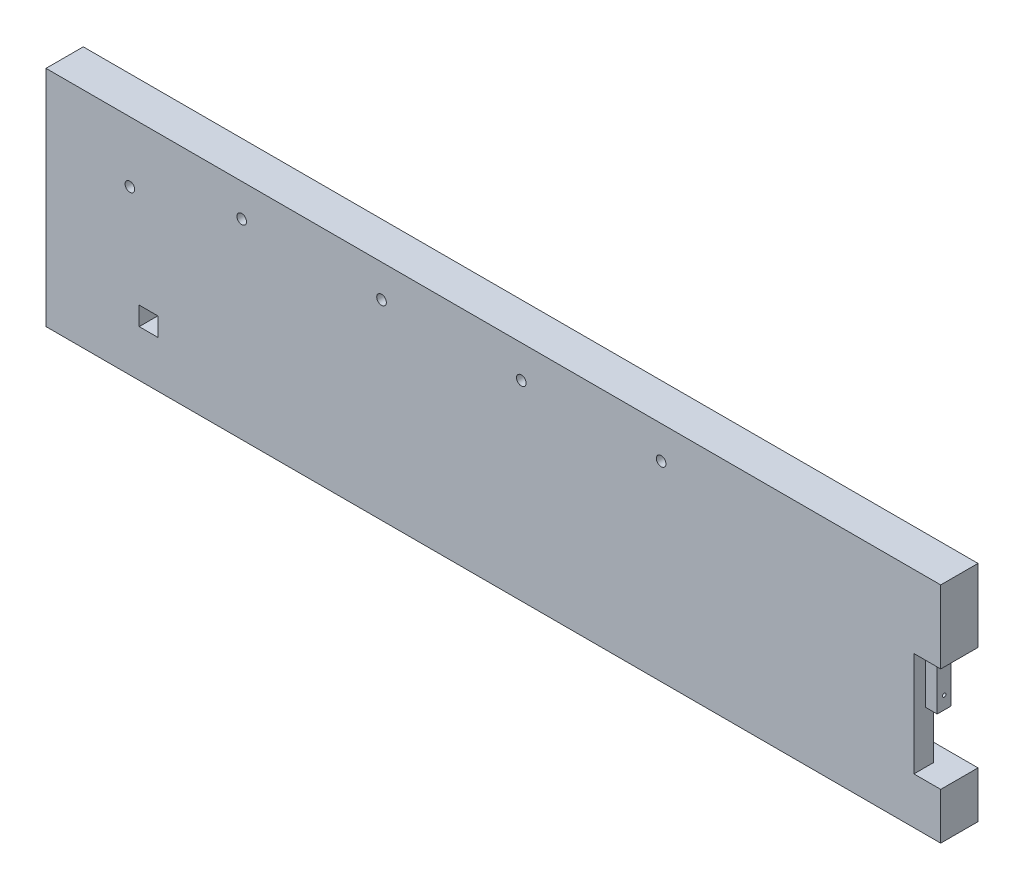
SolidWorks part; units mm, degrees
material "Pine"
ref_plane "Front Plane" through (0, 0, 0) normal (0, 0, 1) x (1, 0, 0)
ref_plane "Top Plane" through (0, 0, 0) normal (0, 1, 0) x (1, 0, 0)
ref_plane "Right Plane" through (0, 0, 0) normal (1, 0, 0) x (0, 0, -1)
sketch "Sketch1" plane through (0, 0, 0) normal (0, 0, 1) x (1, 0, 0)
  line L1 (1219.2, 304.8) -> (-1219.2, 304.8)
  line L2 (1219.2, 304.8) -> (1219.2, -304.8)
  line L3 (1219.2, -304.8) -> (-1219.2, -304.8)
  line L4 (-1219.2, 304.8) -> (-1219.2, -304.8)
  line L5 (1219.2, 304.8) -> (-1219.2, -304.8) construction
  line L6 (1219.2, -304.8) -> (-1219.2, 304.8) construction
  line L7 (-965.2, -127) -> (-914.4, -127)
  line L8 (-965.2, -127) -> (-965.2, -177.8)
  line L9 (-965.2, -177.8) -> (-914.4, -177.8)
  line L10 (-914.4, -127) -> (-914.4, -177.8)
  line L11 (-965.2, -127) -> (-914.4, -177.8) construction
  line L12 (-965.2, -177.8) -> (-914.4, -127) construction
  circle A0 centre (-990.6, 139.7) radius 13.1198
  circle A1 centre (-685.8, 215.9) radius 13.1198
  circle A2 centre (-304.8, 215.9) radius 13.1198
  circle A3 centre (76.2, 215.9) radius 13.1198
  circle A4 centre (457.2, 215.9) radius 13.1198
  point P0 (0, 0)
  point P10 (-939.8, -152.4)
  dimension "D10" = 381
  dimension "D11" = 381
  dimension "D12" = 381
  dimension "D1" = 609.6
  dimension "D2" = 2438.4
  dimension "D3" = 88.9
  dimension "D4" = 228.6
  dimension "D5" = 304.8
  dimension "D6" = 165.1
  dimension "D7" = 127
  dimension "D8" = 50.8
  dimension "D9" = 254
extrude "Boss-Extrude1" add sketch "Sketch1" along normal blind 101.6
sketch "Sketch2" plane through (0, 0, 0) normal (0, 0, -1) x (-1, 0, 0)
  line L0 (1219.2, -304.8) -> (-1219.2, -304.8) construction
  line L1 (711.2, -288.925) -> (-711.2, -288.925)
  line L2 (711.2, -288.925) -> (711.2, -273.05)
  line L3 (711.2, -273.05) -> (-711.2, -273.05)
  line L4 (-711.2, -288.925) -> (-711.2, -273.05)
  line L5 (711.2, -288.925) -> (-711.2, -273.05) construction
  line L6 (711.2, -273.05) -> (-711.2, -288.925) construction
  line L7 (1219.2, 304.8) -> (1219.2, -304.8) construction
  line L9 (711.2, -273.05) -> (838.2, -273.05)
  line L10 (711.2, -273.05) -> (711.2, -209.55)
  line L11 (711.2, -209.55) -> (838.2, -209.55)
  line L12 (838.2, -273.05) -> (838.2, -209.55)
  line L13 (711.2, -273.05) -> (838.2, -209.55) construction
  line L14 (711.2, -209.55) -> (838.2, -273.05) construction
  line L15 (838.2, 209.55) -> (711.2, 209.55)
  line L16 (838.2, 209.55) -> (838.2, 273.05)
  line L17 (838.2, 273.05) -> (711.2, 273.05)
  line L18 (711.2, 209.55) -> (711.2, 273.05)
  line L19 (838.2, 209.55) -> (711.2, 273.05) construction
  line L20 (838.2, 273.05) -> (711.2, 209.55) construction
  line L21 (-838.2, -273.05) -> (-711.2, -273.05)
  line L22 (-838.2, -273.05) -> (-838.2, -209.55)
  line L23 (-838.2, -209.55) -> (-711.2, -209.55)
  line L24 (-711.2, -273.05) -> (-711.2, -209.55)
  line L25 (-838.2, -273.05) -> (-711.2, -209.55) construction
  line L26 (-838.2, -209.55) -> (-711.2, -273.05) construction
  line L27 (-711.2, 209.55) -> (-838.2, 209.55)
  line L28 (-711.2, 209.55) -> (-711.2, 273.05)
  line L29 (-711.2, 273.05) -> (-838.2, 273.05)
  line L30 (-838.2, 209.55) -> (-838.2, 273.05)
  line L31 (-711.2, 209.55) -> (-838.2, 273.05) construction
  line L32 (-711.2, 273.05) -> (-838.2, 209.55) construction
  point P0 (0, -280.9875)
  point P9 (774.7, -241.3)
  point P14 (774.7, 241.3)
  point P19 (-774.7, -241.3)
  point P24 (-774.7, 241.3)
  point P29 (711.2, -241.3)
  dimension "D1" = 15.875
  dimension "D2" = 15.875
  dimension "D3" = 508
  dimension "D4" = 1422.4
  dimension "D5" = 95.25
  dimension "D6" = 508
  dimension "D7" = 15.875
  dimension "D8" = 419.1
  dimension "D9" = 15.875
  dimension "D10" = 127
  dimension "D11" = 63.5
  dimension "D12" = 127
  dimension "D13" = 63.5
  dimension "D14" = 63.5
  dimension "D15" = 127
extrude "Cut-Extrude1" cut sketch "Sketch2" against normal blind 50.8 contours L18 L15 L16 L17 | L9 L12 L11 L10 | L30 L27 L28 L29 | L21 L24 L23 L22 region at (774.7, -241.3, 0) region at (-774.7, -241.3, 0) region at (-774.7, 241.3, 0) region at (774.7, 241.3, 0)
sketch "Sketch3" plane through (0, -304.8, 0) normal (0, -1, 0) x (1, 0, 0)
  line L0 (711.2, 0) -> (838.2, 0) construction
  line L1 (838.2, 0) -> (838.2, 50.8) construction
  line L2 (838.2, 50.8) -> (711.2, 50.8) construction
  line L3 (711.2, 50.8) -> (711.2, 0) construction
  line L4 (-838.2, 0) -> (-711.2, 0) construction
  line L5 (-711.2, 0) -> (-711.2, 50.8) construction
  line L6 (-711.2, 50.8) -> (-838.2, 50.8) construction
  line L7 (-838.2, 50.8) -> (-838.2, 0) construction
  line L8 (711.2, 0) -> (838.2, 0)
  line L9 (838.2, 0) -> (838.2, 50.8)
  line L10 (838.2, 50.8) -> (711.2, 50.8)
  line L11 (711.2, 50.8) -> (711.2, 0)
  line L12 (-838.2, 0) -> (-711.2, 0)
  line L13 (-711.2, 0) -> (-711.2, 50.8)
  line L14 (-711.2, 50.8) -> (-838.2, 50.8)
  line L15 (-838.2, 50.8) -> (-838.2, 0)
  line L16 (-838.2, 25.4) -> (-711.2, 25.4) construction
  line L17 (711.2, 25.4) -> (838.2, 25.4) construction
  circle A0 centre (-742.95, 25.4) radius 4.7625
  circle A1 centre (-806.45, 25.4) radius 4.7625
  circle A2 centre (742.95, 25.4) radius 4.7625
  circle A3 centre (806.45, 25.4) radius 4.7625
  point P14 (-774.7, 25.4)
  point P21 (774.7, 25.4)
  dimension "D1" = 9.525
  dimension "D4" = 9.525
  dimension "D2" = 31.75
  dimension "D3" = 31.75
  dimension "D5" = 31.75
  dimension "D6" = 31.75
extrude "Cut-Extrude2" cut sketch "Sketch3" against normal blind 152.4 contours A3 | A2 | A0 | A1 region at (-742.95, -304.8, 25.4) region at (-806.45, -304.8, 25.4) region at (742.95, -304.8, 25.4) region at (806.45, -304.8, 25.4)
sketch "Sketch4" plane through (0, 0, 101.6) normal (0, 0, 1) x (1, 0, 0)
  line L0 (-1219.2, -304.8) -> (1219.2, -304.8) construction
  line L1 (1219.2, -177.8) -> (1146.175, -177.8)
  line L2 (1219.2, -177.8) -> (1219.2, 106.3625)
  line L3 (1219.2, 106.3625) -> (1146.175, 106.3625)
  line L4 (1146.175, -177.8) -> (1146.175, 106.3625)
  line L5 (1219.2, -304.8) -> (1219.2, 304.8) construction
  point P5 (0, 0)
  dimension "D1" = 73.025
  dimension "D2" = 284.1625
  dimension "D3" = 127
extrude "Cut-Extrude3" cut sketch "Sketch4" against normal through all
sketch "Sketch5" plane through (1146.175, 0, 0) normal (1, 0, 0) x (0, 0, -1)
  line L0 (-46.0375, 71.4375) -> (-46.0375, 76.2) construction
  line L1 (-55.5625, 76.2) -> (-55.5625, 71.4375) construction
  line L2 (-46.0375, 71.4375) -> (-46.0375, 76.2)
  line L3 (-55.5625, 76.2) -> (-55.5625, 71.4375)
  line L4 (-69.85, 87.3125) -> (-69.85, -36.5125)
  line L5 (-31.75, 87.3125) -> (-69.85, 87.3125)
  line L6 (-31.75, -36.5125) -> (-31.75, 87.3125)
  line L7 (-69.85, -36.5125) -> (-31.75, -36.5125)
  line L8 (-69.85, 87.3125) -> (-69.85, -36.5125)
  line L9 (-31.75, 87.3125) -> (-69.85, 87.3125)
  line L10 (-31.75, -36.5125) -> (-31.75, 87.3125)
  line L11 (-69.85, -36.5125) -> (-31.75, -36.5125)
  circle A0 centre (-50.8, -1.5875) radius 4.7625 construction
  arc A1 (-55.5625, 71.4375) -> (-46.0375, 71.4375) centre (-50.8, 71.4375) ccw construction
  arc A2 (-46.0375, 76.2) -> (-55.5625, 76.2) centre (-50.8, 76.2) ccw construction
  circle A3 centre (-50.8, -1.5875) radius 4.7625
  arc A4 (-55.5625, 71.4375) -> (-46.0375, 71.4375) centre (-50.8, 71.4375) ccw
  arc A5 (-46.0375, 76.2) -> (-55.5625, 76.2) centre (-50.8, 76.2) ccw
  dimension "D1" = 0
extrude "Boss-Extrude2" add sketch "Sketch5" along normal blind 31.75 contours A3 | L2 A5 L3 A4 | L11 L10 L9 L8 region at (1146.175, 73.8188, 50.8) region at (1146.175, -1.5875, 50.8)
sketch "Sketch8" plane through (1146.175, 0, 0) normal (1, 0, 0) x (0, 0, -1)
  line L0 (-69.85, -36.5125) -> (-31.75, -36.5125) construction
  line L1 (0, -177.8) -> (-47.625, -177.8)
  line L2 (0, -177.8) -> (0, -36.5125)
  line L3 (0, -36.5125) -> (-47.625, -36.5125)
  line L4 (-47.625, -177.8) -> (-47.625, -36.5125)
  line L5 (0, 106.3625) -> (0, -177.8) construction
  line L6 (0, -36.5125) -> (-6.35, -36.5125) construction
  line L7 (-6.35, -36.5125) -> (-6.35, -17.4625) construction
  line L8 (0, -17.4625) -> (-6.35, -17.4625) construction
  line L9 (0, -158.75) -> (-6.35, -158.75) construction
  line L10 (0, -139.7) -> (-6.35, -139.7) construction
  line L11 (-6.35, -158.75) -> (-6.35, -139.7) construction
  line L12 (0, -36.5125) -> (-6.35, -36.5125)
  line L13 (-6.35, -36.5125) -> (-6.35, -17.4625)
  line L14 (0, -17.4625) -> (-6.35, -17.4625)
  line L15 (0, -158.75) -> (-6.35, -158.75)
  line L16 (0, -139.7) -> (-6.35, -139.7)
  line L17 (-6.35, -158.75) -> (-6.35, -139.7)
  line L18 (0, -36.5125) -> (0, -17.4625)
  line M5 (-31.75, -36.5125) -> (-69.85, -36.5125)
  line M7 (-101.6, -177.8) -> (0, -177.8)
  line M8 (0, -177.8) -> (0, 106.3625)
  dimension "D1" = 47.625
extrude "Cut-Extrude4" cut sketch "Sketch8" against normal blind 431.8 contours L15 L17 L16 L3 L4 M8 M5 M7 | L17 L15 L2 L16 | L14 L13 L3 M8 region at (1146.175, -106.3861, 24.1903) region at (1146.175, -149.225, 3.175) region at (1146.175, -26.9875, 3.175)
